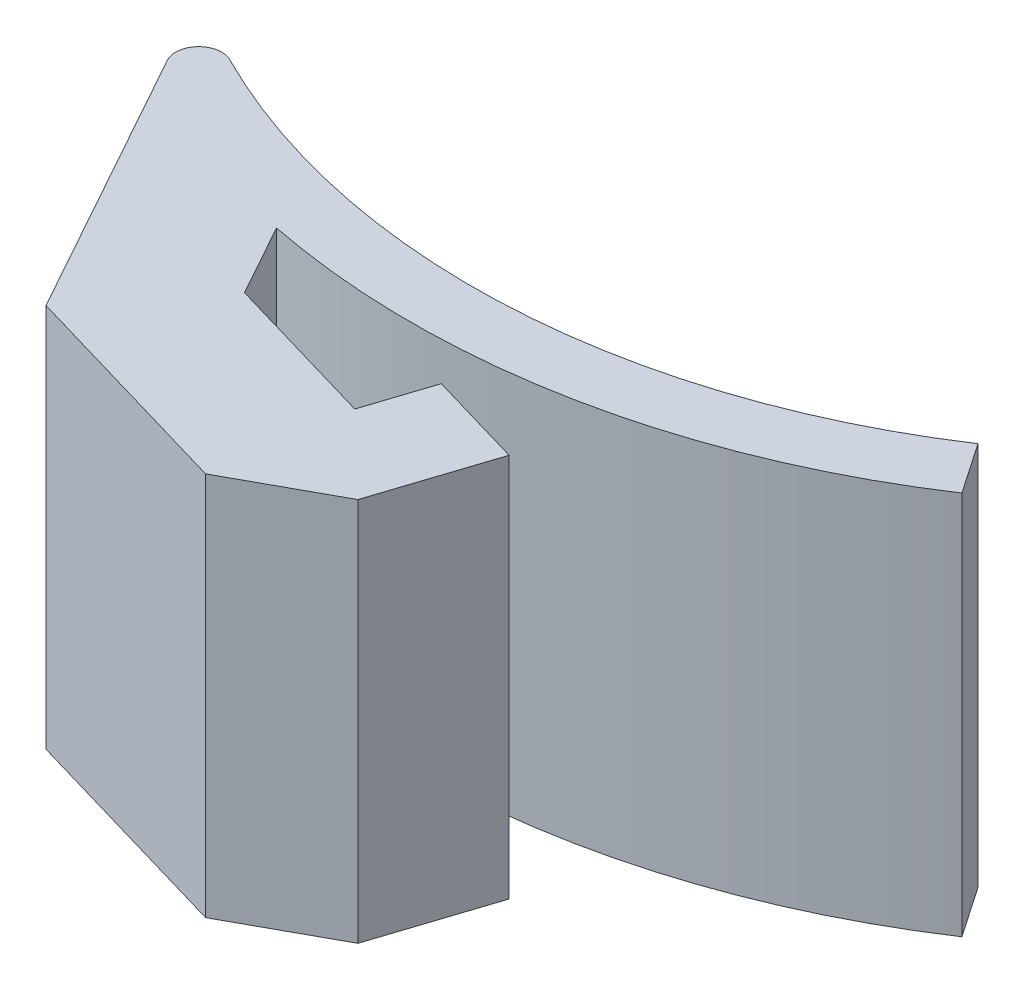
SolidWorks part; units mm, degrees
ref_plane "Спереди" through (0, 0, 0) normal (0, 0, 1) x (1, 0, 0)
ref_plane "Сверху" through (0, 0, 0) normal (0, 1, 0) x (1, 0, 0)
ref_plane "Справа" through (0, 0, 0) normal (1, 0, 0) x (0, 0, -1)
sketch "Эскиз1" plane through (0, 0, 0) normal (0, 1, 0) x (1, 0, 0)
  line L0 (4.2452, -5.0108) -> (4.7271, -3.3642) construction
  line L1 (2.5, -4.5) -> (6.3951, -5.64)
  line L2 (6.3951, -5.64) -> (7.2, -3.175)
  line L3 (7.2, -3.175) -> (5.9523, -2.8099)
  line L4 (5.9523, -2.8099) -> (5.6754, -3.658)
  line L5 (5.6754, -3.658) -> (3.6472, -3.0644)
  line L6 (3.6472, -3.0644) -> (3.1268, -2.1278)
  line L7 (10.12, 0.0055) -> (10.5711, -0.6553)
  line L9 (0.5267, -0.9481) -> (2.5, -4.5)
  line L10 (2.1224, -3.8203) -> (3.5998, -2.9995) construction
  arc A0 (0.9239, -0.5345) -> (10.12, 0.0055) centre (5.0558, 7.6737) ccw
  arc A1 (3.1268, -2.1278) -> (10.5711, -0.6553) centre (5.0558, 7.6737) ccw
  arc A3 (-0.4009, -0.6938) -> (10.5609, -0.6621) centre (5.0558, 7.6737) ccw construction
  arc A4 (0.0361, -0.0237) -> (10.12, 0.0055) centre (5.0558, 7.6737) ccw construction
  arc A5 (0.9239, -0.5345) -> (0.5267, -0.9481) centre (0.789, -0.8024) ccw
  point P12 (3.1251, -2.9116)
  point P14 (3.6084, -2.9947)
  point P18 (5.5945, -1.5)
  point P25 (4.7228, -3.3792)
  point P26 (0, 0)
  dimension "D8" = 0.3
  dimension "D1" = 10.12
  dimension "D2" = 1.7
  dimension "D3" = 4.5
  dimension "D4" = 2.5
  dimension "D5" = 7.2
  dimension "D6" = 5.64
  dimension "D7" = 1.3
  dimension "D9" = 1.7
  dimension "D11" = 1.5
  dimension "D12" = 0.8
extrude "Бобышка-Вытянуть1" add sketch "Эскиз1" along normal blind 5
chamfer "Фаска1" distance 1 angle 45 1 edges at (6.3951, 2.5, 5.64) first distance on face at (4.4475, 2.5, 5.07)
